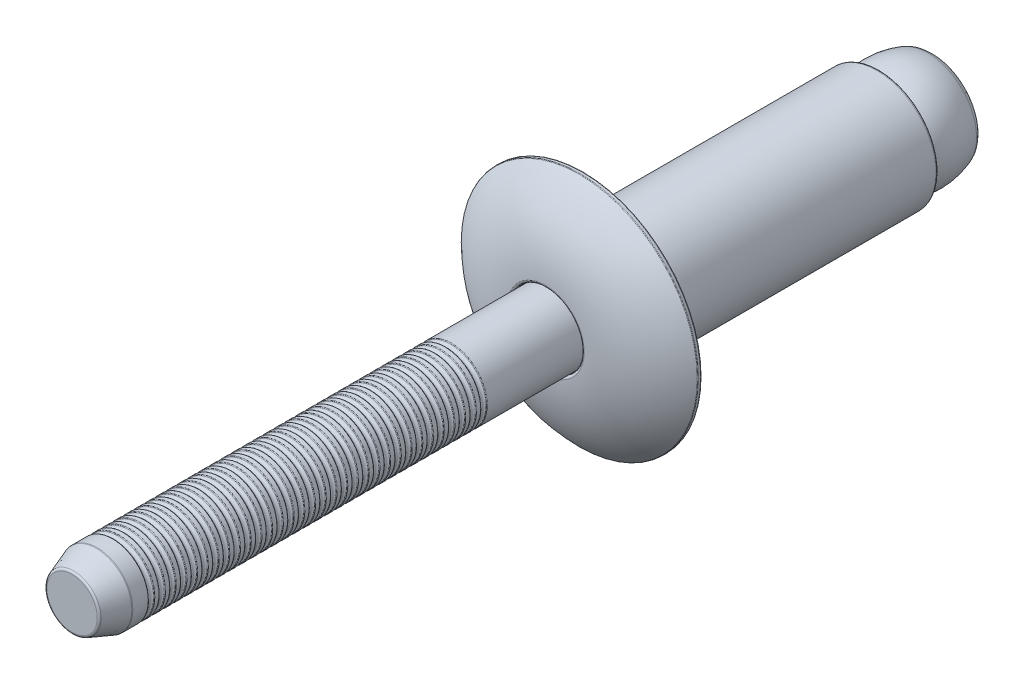
SolidWorks part; units mm, degrees
ref_plane "Front Plane" through (0, 0, 0) normal (0, 0, 1) x (1, 0, 0)
ref_plane "Top Plane" through (0, 0, 0) normal (0, 1, 0) x (1, 0, 0)
ref_plane "Right Plane" through (0, 0, 0) normal (1, 0, 0) x (0, 0, -1)
sketch "Sketch1" plane through (0, 0, 0) normal (1, 0, 0) x (0, 0, -1)
  line L0 (-23.3997, 0) -> (23.3998, 0) construction
  line L1 (19.9073, 0) -> (19.9073, 3.175)
  line L2 (4.0323, 0) -> (4.0323, 6.35)
  line L3 (4.0323, 6.35) -> (3.8291, 6.35)
  line L4 (2.0003, 1.9177) -> (-23.3997, 1.9177)
  line L5 (-23.3997, 1.9177) -> (-23.3997, 0)
  line L6 (2.0003, 1.9177) -> (2.0003, 6.35) construction
  line L7 (19.9073, 3.175) -> (20.7804, 3.175)
  line L8 (20.7804, 3.175) -> (21.6535, 3.175)
  line L9 (21.6535, 3.175) -> (22.5266, 3.175)
  line L10 (22.5266, 3.175) -> (23.3998, 3.175)
  line L11 (19.9073, 3.175) -> (4.0323, 3.175)
  line L12 (-23.3997, 0) -> (-23.3997, -1.9177)
  arc A0 (3.8291, 6.35) -> (2.0003, 1.9177) centre (8.2857, 1.9177) ccw
  ellipse E0 centre (20.7804, 0) end of major axis (20.7804, 3.175) minor radius 2.6194 (19.9073, 2.9934) -> (23.3998, 0) cw
  point P1 (-3.0797, 1.9177)
  point P2 (0, 0)
  point P18 (23.3998, 3.175)
  point P24 (23.3998, -3.175)
  point P28 (-23.3997, 1.9177)
  point P30 (-23.3997, -1.9177)
  dimension "Length" = 15.875
  dimension "D1" = 3.4925
  dimension "Head Height" = 2.032
  dimension "D2" = 0.2032
  dimension "Head Diameter" = 12.7
  dimension "Mandrel Length" = 25.4
  dimension "Diameter" = 6.35
  dimension "Mandrel OD" = 3.8354
  dimension "D5" = 20.32
sketch "Sketch2" plane through (0, 0, 0) normal (1, 0, 0) x (0, 0, -1)
  line L0 (-23.3997, 0) -> (-23.3997, 1.9177)
  line L1 (-23.3997, 1.9177) -> (2.0003, 1.9177)
  line L2 (4.0323, 6.35) -> (3.8291, 6.35) construction
  line L3 (4.0323, 6.35) -> (3.8291, 6.35)
  line L4 (4.0323, 6.35) -> (4.0323, 3.175)
  line L5 (4.0323, 3.175) -> (19.9073, 3.175)
  line L6 (19.9073, 3.175) -> (19.9073, 2.8575)
  line L7 (23.3998, 0) -> (-23.3997, 0)
  line L8 (19.9073, 2.8575) -> (19.5897, 2.54)
  line L9 (19.5897, 2.54) -> (19.9073, 2.54) construction
  line L10 (-23.3997, 0) -> (23.3998, 0) construction
  line L11 (23.3998, 0) -> (19.9073, 0) construction
  line L12 (19.9073, 0) -> (19.9073, 3.175) construction
  line L13 (23.3998, 2.8575) -> (19.9073, 2.8575) construction
  line L14 (23.3998, 2.8575) -> (23.3998, 0) construction
  line L15 (22.7189, 2.54) -> (23.3998, 2.8575) construction
  line L16 (2.0003, 1.9177) -> (3.8291, 1.9177)
  line L17 (3.8291, 1.9177) -> (3.8291, 1.9431)
  line L18 (3.8291, 1.9431) -> (2.0003, 1.9431)
  arc A3 (22.7189, 2.54) -> (23.3998, 0) centre (18.3216, 0) cw
  arc A4 (19.5897, 2.54) -> (22.7189, 2.54) centre (21.1543, -1.1561) cw
  arc A5 (3.8291, 6.35) -> (2.0003, 1.9177) centre (8.2857, 1.9177) ccw construction
  arc A6 (2.0003, 1.9431) -> (3.8291, 6.35) centre (8.2857, 1.9177) cw
  dimension "D1" = 45
  dimension "D2" = 5.08
  dimension "D3" = 5.715
  dimension "D4" = 25
  dimension "D5" = 0.0254
revolve "Revolve1" add sketch "Sketch2" angle 360 about L7
sketch "Sketch7" plane through (0, 0, -4.0323) normal (0, 0, -1) x (-1, 0, 0)
  circle A0 centre (0, 0) radius 4.7625
  circle A1 centre (0, 0) radius 3.175 construction
  circle A2 centre (0, 0) radius 3.175
  dimension "D1" = 9.525
extrude "Cut-Extrude1" cut sketch "Sketch7" against normal blind 0.2032
sketch "Sketch8" plane through (0, 0, 0) normal (1, 0, 0) x (0, 0, -1)
  line L0 (-23.3997, 1.4383) -> (-22.0825, 1.9177)
  line L1 (-23.3997, 1.9177) -> (-23.3997, 0) construction
  line L2 (2.0003, 1.9177) -> (-23.3997, 1.9177) construction
  line L3 (-22.0825, 1.9177) -> (-23.3997, 1.9177)
  line L4 (-23.3997, 1.9177) -> (-23.3997, 1.4383)
  line L5 (-23.3997, 0) -> (0, 0) construction
  line L6 (-23.3997, 0) -> (23.3998, 0) construction
  dimension "D1" = 2.8765
  dimension "D2" = 20
revolve "Cut-Revolve3" cut sketch "Sketch8" angle 360 about L5
fillet "Fillet1" radius 0.127 6 edges at (0, 2.8575, -19.9073) (0, 3.175, -19.9073) (0, 1.9431, -2.0003) (0, 3.175, -3.8291) (0, -1.4383, 23.3997) (0, -1.9177, 22.0825)
fillet "Fillet2" radius 0.5715 1 edges at (0, 2.54, -22.7189)
fillet "Fillet3" radius 0.061 2 edges at (0, 6.35, -3.8291) (0, 6.35, -4.0323)
chamfer "Chamfer1" distance 0.2032 angle 45 1 edges at (0, 4.7625, -3.8291)
sketch "Sketch6" plane through (0, 0, 0) normal (1, 0, 0) x (0, 0, -1)
  line L0 (2.0003, 1.9177) -> (-23.3997, 1.9177) construction
  line L1 (-23.3997, 0) -> (23.3998, 0) construction
  line L2 (-23.3997, 0) -> (23.3998, 0) construction
  circle A0 centre (-3.2236, 1.9177) radius 0.1438
  point P6 (-3.0797, 1.9177)
  dimension "D1" = 0.2877
revolve "Cut-Revolve2" cut sketch "Sketch6" angle 360 about L2
fillet "Fillet4" radius 0.0381 2 edges at (0, 1.9177, 3.3674) (0, -1.9177, 3.0797)
pattern_linear "LPattern2" count 32 spacing 0.5753 along (0, 0, 1) of "Cut-Revolve2", "Fillet4"
equation "\"D2@Sketch1\"=\"Head Height@Sketch1\"*0.1"
equation "\"D1@Sketch1\"=\"Diameter@Sketch1\"*0.55"
equation "\"D1@Sketch6\"=\"Mandrel OD@Sketch1\" * .075"
equation "\"D5@Sketch1\"=\"Mandrel Length@Sketch1\" * 0.8"
equation "\"D3@LPattern2\"=\"D1@Sketch6\"*2"
equation "\"D5@LPattern2\"=\"D1@Sketch6\""
equation "\"D2@Sketch2\"=\"Diameter@Sketch1\"*0.8"
equation "\"D3@Sketch2\"=\"Diameter@Sketch1\" * 0.9"
equation "\"D1@Fillet1\"=\"Diameter@Sketch1\"*0.05*0.4"
equation "\"D1@Fillet2\"=\"D3@Sketch2\"*0.1"
equation "\"D1@Sketch7\"=\"Head Diameter@Sketch1\"*.75"
equation "\"D1@Cut-Extrude1\"=\"D2@Sketch1\""
equation "\"D1@Fillet3\"=\"D2@Sketch1\"*.3"
equation "\"D1@Sketch8\"=\"Mandrel OD@Sketch1\"*0.75"
equation "\"D1@LPattern2\"=\"D5@Sketch1\"*0.9/\"D3@LPattern2\""
equation "\"D1@Fillet4\"=\"D1@Fillet1\"*.3"
equation "\"D1@Chamfer1\"=\"D2@Sketch1\""
